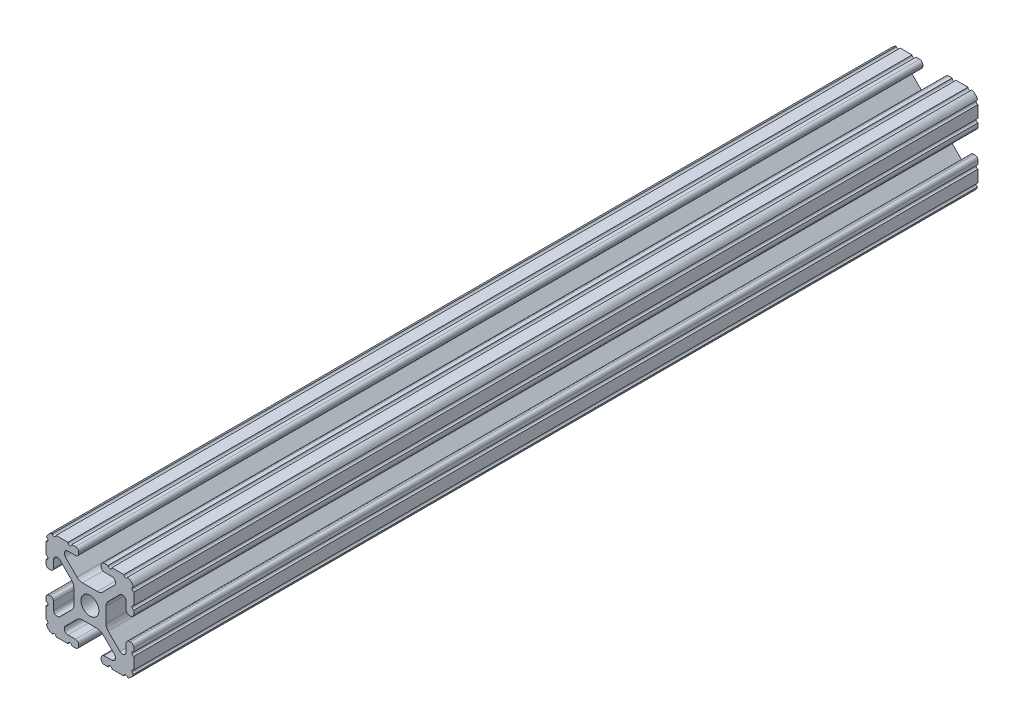
SolidWorks part; units mm, degrees
ref_plane "Front Plane" through (0, 0, 0) normal (0, 0, 1) x (1, 0, 0)
ref_plane "Top Plane" through (0, 0, 0) normal (0, 1, 0) x (1, 0, 0)
ref_plane "Right Plane" through (0, 0, 0) normal (1, 0, 0) x (0, 0, -1)
sketch "Sketch2" plane through (0, 0, 0) normal (0, 0, 1) x (1, 0, 0)
  line L0 (0, 12.7) -> (0, -12.7) construction
  line L1 (-12.7, 0) -> (12.7, 0) construction
  line L2 (3.2512, -12.7) -> (12.7, -12.7)
  line L3 (12.7, -12.7) -> (12.7, -3.2512)
  line L4 (3.2512, -12.7) -> (3.2512, -10.4902)
  line L5 (3.2512, -10.4902) -> (8.9276, -10.4902)
  line L6 (8.9276, -10.4902) -> (3.0856, -4.6482)
  line L7 (0, 0) -> (12.7, -12.7) construction
  line L8 (12.7, -3.2512) -> (10.4902, -3.2512)
  line L9 (10.4902, -3.2512) -> (10.4902, -8.9276)
  line L10 (10.4902, -8.9276) -> (4.6482, -3.0856)
  circle A0 centre (0, 0) radius 2.6035
  arc A1 (6.3485, -10.4902) -> (7.1039, -8.6665) centre (6.3485, -9.4219) ccw construction
  point P8 (0, -4.6482)
  dimension "Center Hole Diameter" = 5.207
  dimension "Rail Height" = 25.4
  dimension "Rail Width" = 25.4
  dimension "T-Slot Width" = 6.5024
  dimension "Slot Inner Width" = 14.8336
  dimension "Thickness" = 2.2098
  dimension "Slot Depth" = 5.842
  dimension "D1" = 2.2098
sketch "Sketch3" plane through (0, 0, 0) normal (1, 0, 0) x (0, 0, -1)
  line L0 (-122.0614, -12.7) -> (122.0614, -12.7) construction
  line L1 (-96.6614, 0) -> (96.6614, 0) construction
  line L3 (122.0614, 0) -> (-122.0614, 0) construction
sketch "Sketch4" plane through (0, 0, 0) normal (0, 0, 1) x (1, 0, 0)
  line L0 (4.1904, -12.7) -> (10.1173, -12.7)
  line L1 (3.2512, -12.7) -> (12.7, -12.7) construction
  line L2 (3.2512, -12.7) -> (3.2512, -10.4902) construction
  line L3 (3.2512, -10.4902) -> (8.9276, -10.4902) construction
  line L4 (3.2512, -11.4294) -> (3.2512, -11.7608)
  line L5 (4.1904, -10.4902) -> (6.3485, -10.4902)
  line L6 (0, -4.6482) -> (2.164, -4.6482)
  line L7 (8.9276, -10.4902) -> (3.0856, -4.6482) construction
  line L8 (3.7373, -5.2999) -> (7.1039, -8.6665)
  line L9 (12.7, -12.7) -> (12.7, -3.2512) construction
  line L10 (10.4902, -8.9276) -> (4.6482, -3.0856) construction
  line L11 (10.4902, -3.2512) -> (10.4902, -8.9276) construction
  line L12 (10.4902, -6.3485) -> (10.4902, -4.1904)
  line L13 (12.7, -3.2512) -> (10.4902, -3.2512) construction
  line L14 (11.4294, -3.2512) -> (11.7608, -3.2512)
  line L15 (12.7, -4.1904) -> (12.7, -10.1173)
  line L16 (8.6665, -7.1039) -> (5.2999, -3.7373)
  line L17 (4.6482, 0) -> (4.6482, -2.164)
  line L18 (-12.7, 0) -> (12.7, 0) construction
  line L19 (0, -4.6482) -> (0, -2.6035)
  line L20 (0, 12.7) -> (0, -12.7) construction
  line L21 (4.6482, 0) -> (2.6035, 0)
  arc A0 (3.2512, -11.7608) -> (4.1904, -12.7) centre (4.1904, -11.7608) ccw
  arc A2 (3.2512, -11.4294) -> (4.1904, -10.4902) centre (4.1904, -11.4294) cw
  arc A3 (6.3485, -10.4902) -> (7.1039, -8.6665) centre (6.3485, -9.4219) ccw
  arc A4 (2.164, -4.6482) -> (3.7373, -5.2999) centre (2.164, -6.8732) cw
  arc A5 (10.1173, -12.7) -> (12.7, -10.1173) centre (10.1173, -10.1173) ccw
  arc A6 (8.6665, -7.1039) -> (10.4902, -6.3485) centre (9.4219, -6.3485) ccw
  arc A7 (10.4902, -4.1904) -> (11.4294, -3.2512) centre (11.4294, -4.1904) cw
  arc A8 (11.7608, -3.2512) -> (12.7, -4.1904) centre (11.7608, -4.1904) cw
  arc A9 (5.2999, -3.7373) -> (4.6482, -2.164) centre (6.8732, -2.164) cw
  circle A10 centre (0, 0) radius 2.6035 construction
  arc A11 (0, -2.6035) -> (2.6035, 0) centre (0, 0) ccw
  dimension "D1" = 2.5827
  dimension "D2" = 2.225
  dimension "D3" = 0.9392
extrude "Boss-Extrude1" add sketch "Sketch4" along normal up to vertex (122.0614 mm away) from vertex up to point (0, -12.7, 122.0614) starting at point (0, -12.7, -122.0614)
sketch "Sketch5" plane through (0, 0, 0) normal (0, 0, 1) x (1, 0, 0)
  line L0 (3.2512, -12.7) -> (12.7, -12.7) construction
  line L1 (4.1904, -10.4902) -> (6.3485, -10.4902) construction
  line L3 (0, 0) -> (12.7, -12.7) construction
  line L4 (6.3485, -10.4902) -> (6.3485, -12.7) construction
  line L5 (8.9276, -10.4902) -> (3.0856, -4.6482) construction
  circle A0 centre (10.3562, -12.7) radius 0.5524
  circle A1 centre (5.796, -12.7) radius 0.5524
  circle A2 centre (12.7, -10.3562) radius 0.5524
  circle A3 centre (12.7, -5.796) radius 0.5524
  point P10 (5.2694, -10.4902)
  point P12 (9.4219, -6.3485)
  dimension "D1" = 1.1049
extrude "Cut-Extrude1" cut sketch "Sketch5" against normal through all both and the other way through all
mirror "Mirror1" about plane through (0, 0, 0) normal (1, 0, 0) of bodies 137 134
mirror "Mirror2" about plane through (0, 0, 0) normal (0, 1, 0) of bodies 135
equation "\"D1@Sketch2\"=\"Thickness@Sketch2\""
equation "\"D2@Sketch4\"=\"Slot Inner Width@Sketch2\"*0.15"
equation "\"D1@Sketch4\"=\"D3@Sketch4\"*2.75"
equation "\"D3@Sketch4\"=\"Thickness@Sketch2\"*0.425"
equation "\"D1@Sketch5\"=\"Thickness@Sketch2\"*0.5"
equation "\"D1@Boss-Extrude1\"=\"Length@Sketch3\""
